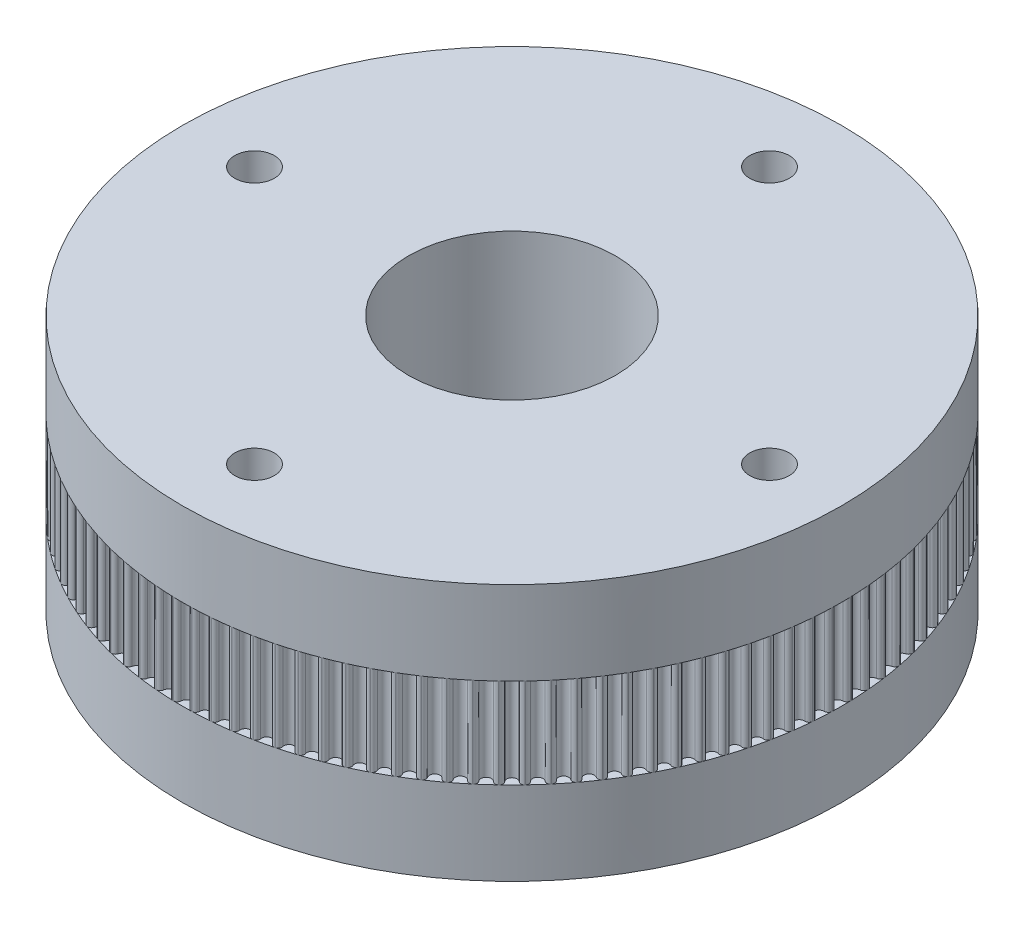
SolidWorks part; units mm, degrees
ref_plane "Front plan" through (0, 0, 0) normal (0, 0, 1) x (1, 0, 0)
ref_plane "Top plan" through (0, 0, 0) normal (0, 1, 0) x (1, 0, 0)
ref_plane "Right plan" through (0, 0, 0) normal (1, 0, 0) x (0, 0, -1)
sketch "Skica2" plane through (0, 0, 0) normal (0, 0, 1) x (1, 0, 0)
  line L1 (11, 4.775) -> (11, -4.775)
  line L3 (0, -9) -> (0, 9) construction
  line L7 (36, 3.775) -> (35, 3.775)
  line L8 (35, 3.775) -> (35, -3.775)
  line L9 (36, 3.775) -> (36, 4.775)
  line L12 (36, -4.775) -> (8.107, -4.775)
  line L13 (36, 4.775) -> (12.5, 4.775)
  line L14 (36, -4.775) -> (36, -3.775)
  line L15 (35, -3.775) -> (36, -3.775)
  line L17 (12.5, 4.775) -> (11, 4.775)
  line L18 (8.107, -4.775) -> (11, -4.775)
  point P3 (11, 0)
  point P7 (0, 0)
  dimension "D3" = 70
  dimension "D1" = 22
  dimension "D2" = 9.55
  dimension "D4" = 1
  dimension "D5" = 1
revolve "Revolute" add sketch "Skica2" angle 360 about L3 region at (23.1081, 0, 0)
sketch "Sketch2" plane through (0, 3.775, 0) normal (0, -1, 0) x (1, 0, 0)
  line L0 (0, 0) -> (0, 34.6075) construction
  line L1 (0, 0) -> (11.8019, 32.9502) construction
  line L3 (0, 0) -> (-2.5216, 34.909) construction
  circle A1 centre (0, 0) radius 34.0575 construction
  circle A2 centre (0, 0) radius 34.6 construction
  arc A3 (-0.5499, 34.5956) -> (0.5499, 34.5956) centre (0, 34.6075) ccw
  arc A7 (-0.9608, 34.9868) -> (-2.5216, 34.909) centre (0, 0) ccw
  arc A8 (0, 36.241) -> (2.5216, 34.909) centre (0.9503, 34.9871) cw
  circle A9 centre (0, 0) radius 35 construction
  arc A10 (0.9608, 34.9868) -> (2.5216, 34.909) centre (0, 0) cw
  arc A11 (0.9608, 34.9868) -> (0.5499, 34.5956) centre (0.9498, 34.587) ccw
  arc A12 (0, 36.241) -> (-2.5216, 34.909) centre (-0.9503, 34.9871) ccw
  arc A13 (-0.9608, 34.9868) -> (-0.5499, 34.5956) centre (-0.9498, 34.587) cw
  dimension "D2" = 0.8
  dimension "D4" = 0.55
  dimension "D6" = 70
  dimension "D3" = 1.5733
  dimension "D1" = 0.4
extrude "Cut-Extrude3" cut sketch "Sketch2" along normal mid plane 50
pattern_circular "CirPattern1" count 112 over 360 about axis through (0, -9, 0) along (0, -1, 0) of "Cut-Extrude3"
sketch "Sketch4" plane through (0, -4.775, 0) normal (0, -1, 0) x (1, 0, 0)
  circle A0 centre (0, 0) radius 20.125
  circle A1 centre (0, 0) radius 7.25
  dimension "D1" = 40.25
  dimension "D2" = 14.5
extrude "Cut-Extrude4" [suppressed] cut sketch "Sketch4" against normal blind 2
ref_plane "Plane1" through (0, 1.575, 0) normal (0, -1, 0) x (-1, 0, 0)
mirror "Mirror1" [suppressed] about plane through (0, 0, 0) normal (0, 1, 0)
sketch "Sketch7" plane through (0, -4.775, 0) normal (0, -1, 0) x (1, 0, 0)
  circle A0 centre (-27.35, 0) radius 2.1
  dimension "D1" = 27.35
  dimension "D2" = 4.2
extrude "Cut-Extrude5" cut sketch "Sketch7" against normal through all
pattern_circular "CirPattern2" count 4 over 270 about axis through (0, -4.775, 0) along (0, -1, 0) of "Cut-Extrude5"
sketch "Sketch8" plane through (0, -4.775, 0) normal (0, -1, 0) x (1, 0, 0)
  circle A0 centre (0, 0) radius 35
  circle A1 centre (-27.35, 0) radius 2.1
  circle A2 centre (0, 27.35) radius 2.1
  circle A3 centre (27.35, 0) radius 2.1
  circle A4 centre (0, -27.35) radius 2.1
  circle A6 centre (0, 0) radius 11
  circle A8 centre (0, 0) radius 11 construction
  circle A9 centre (-27.35, 0) radius 2.1 construction
  circle A10 centre (0, -27.35) radius 2.1 construction
extrude "Boss-Extrude1" add sketch "Sketch8" along normal blind 8.875 contours A0 A4 A3 A2 A1 | A6 region at (-34.0101, -4.775, 0)
mirror "Mirror2" about plane through (0, 0, 0) normal (0, 1, 0) of "Boss-Extrude1"
equation "\"`\"=2"
equation "\"D6@Sketch2\"= \"D3@Skica2\""
